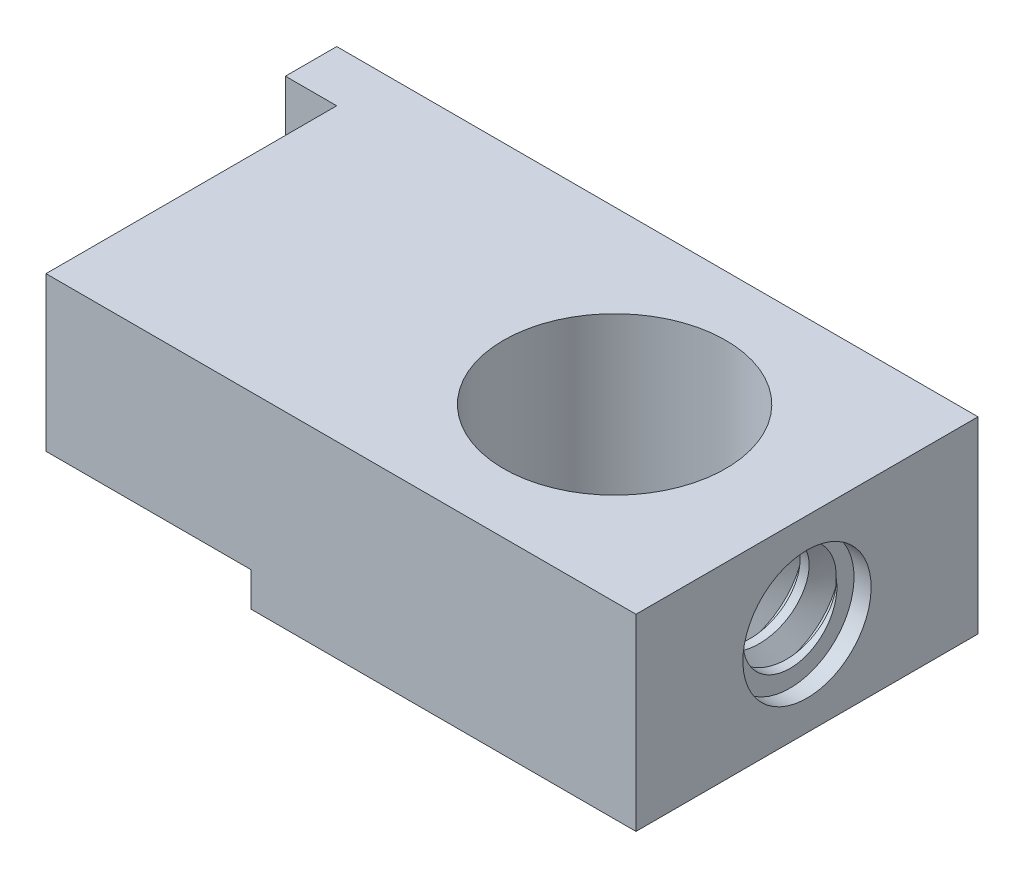
SolidWorks part; units mm, degrees
ref_plane "Front Plane" through (0, 0, 0) normal (0, 0, 1) x (1, 0, 0)
ref_plane "Top Plane" through (0, 0, 0) normal (0, 1, 0) x (1, 0, 0)
ref_plane "Right Plane" through (0, 0, 0) normal (1, 0, 0) x (0, 0, -1)
sketch "Sketch1" plane through (0, 0, 0) normal (0, 0, 1) x (1, 0, 0)
  line L1 (0, 0) -> (-22.5, 0)
  line L2 (0, 0) -> (0, -11)
  line L3 (0, -11) -> (-22.5, -11)
  line L4 (-22.5, 0) -> (-22.5, -11)
  dimension "D1" = 11
  dimension "D2" = 22.5
extrude "Boss-Extrude1" add sketch "Sketch1" along normal blind 20
sketch "Sketch3" plane through (0, 0, 0) normal (0, 1, 0) x (1, 0, 0)
  line L0 (0, -20) -> (-22.5, -20) construction
  line L1 (0, -20) -> (0, 0) construction
  circle A0 centre (-11.25, -10) radius 6.5
  point P4 (-11.25, -20)
  point P7 (0, -10)
  dimension "D1" = 0
  dimension "D2" = 0
  dimension "D3" = 13
extrude "Cut-Extrude1" cut sketch "Sketch3" against normal blind 26
sketch "Sketch4" plane through (0, 0, 0) normal (1, 0, 0) x (0, 0, -1)
  line L0 (-20, 0) -> (0, 0) construction
  line L1 (0, -11) -> (0, 0) construction
  circle A0 centre (-10, -5.5) radius 2.75
  point P4 (-10, 0)
  point P7 (0, -5.5)
  dimension "D1" = 0
  dimension "D2" = 0
  dimension "D3" = 5.5
extrude "Cut-Extrude2" cut sketch "Sketch4" against normal blind 9
sketch "Sketch6" plane through (-22.5, 0, 0) normal (-1, 0, 0) x (0, 0, 1)
  line L0 (20, 0) -> (0, 0) construction
  line L1 (0, -11) -> (3, -11)
  line L2 (0, -11) -> (0, 0)
  line L3 (0, 0) -> (3, 0)
  line L4 (3, -11) -> (3, 0)
  dimension "D1" = 3
extrude "Boss-Extrude4" add sketch "Sketch6" along normal blind 15
thread "Thread1" pitch 2.1167 method cut profile "Thread Profile1" start angle 0, offset 0, length 14, pitch 2.1167, diameter 5.5
ref_plane "Plane1" through (0, -5.5, 12.75) normal (0, -1, 0) x (0, 0, 1)
sketch "Thread Profile1" plane through (0, -5.5, 12.75) normal (0, -1, 0) x (0, 0, 1)
  line L0 (0, 0) -> (0, 2.1167) construction
  line L1 (0, 0) -> (1.1457, 0.6615)
  line L2 (1.1457, 0.6615) -> (1.1457, 0.926)
  line L3 (1.1457, 0.926) -> (0, 1.5875)
  line L4 (1.1457, 0.7937) -> (0, 0.7937) construction
  line L11 (0, 0) -> (0, 1.5875)
  point P2 (0, 0)
  dimension "Pitch" = 2.1167
  dimension "Profile_Angle" = 60
  dimension "Profile_Land" = 0.2646
  dimension "Profile_Height" = 1.1457
sketch "Sketch7" plane through (-22.5, 0, 0) normal (-1, 0, 0) x (0, 0, 1)
  line L0 (3, -11) -> (3, 0) construction
  line L1 (20, 0) -> (3, 0)
  line L2 (20, 0) -> (20, -5)
  line L3 (20, -5) -> (3, -5)
  line L4 (3, 0) -> (3, -5)
  dimension "D1" = 5
extrude "Boss-Extrude5" add sketch "Sketch7" along normal blind 12
sketch "Sketch8" plane through (0, -5, 0) normal (0, -1, 0) x (-1, 0, 0)
  line L0 (34.5, -3) -> (34.5, -20) construction
  line L1 (22.5, -20) -> (34.5, -20)
  line L2 (22.5, -20) -> (22.5, -13.5)
  line L3 (22.5, -13.5) -> (34.5, -13.5)
  line L4 (34.5, -20) -> (34.5, -13.5)
  line L5 (34.5, -3) -> (22.5, -3) construction
  dimension "D1" = 10.5
extrude "Boss-Extrude6" add sketch "Sketch8" along normal blind 4
sketch "Sketch10" plane through (0, -5, 0) normal (0, -1, 0) x (-1, 0, 0)
  line L1 (34.5, -3) -> (32, -3)
  line L2 (34.5, -3) -> (34.5, -13.5)
  line L3 (34.5, -13.5) -> (32, -13.5)
  line L4 (32, -3) -> (32, -13.5)
  line L5 (34.5, -13.5) -> (22.5, -13.5) construction
  dimension "D1" = 0
  dimension "D2" = 2.5
extrude "Boss-Extrude7" add sketch "Sketch10" along normal up to vertex up to point (-22.5, -9, 13.5)
sketch "Sketch11" plane through (0, 0, 0) normal (1, 0, 0) x (0, 0, -1)
  circle A0 centre (-10, -5.5) radius 3.75
  dimension "D1" = 7.5
extrude "Cut-Extrude3" cut sketch "Sketch11" against normal blind 1
